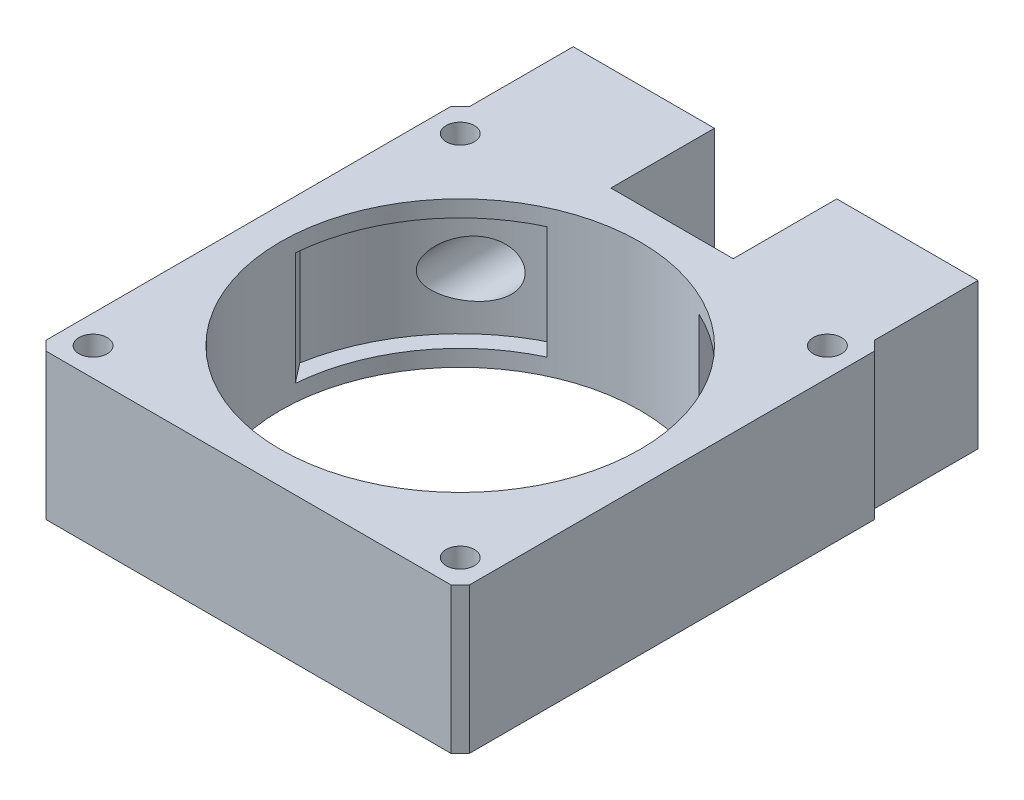
SolidWorks part; units mm, degrees
ref_plane "前视基准面" through (0, 0, 0) normal (0, 0, 1) x (1, 0, 0)
ref_plane "上视基准面" through (0, 0, 0) normal (0, 1, 0) x (1, 0, 0)
ref_plane "右视基准面" through (0, 0, 0) normal (1, 0, 0) x (0, 0, -1)
sketch "草图1" plane through (0, 0, 0) normal (0, 1, 0) x (1, 0, 0)
  line L1 (-22.5, -22.5) -> (22.5, -22.5)
  line L2 (-22.5, -22.5) -> (-22.5, 22.5)
  line L3 (-22.5, 22.5) -> (22.5, 22.5)
  line L4 (22.5, -22.5) -> (22.5, 22.5)
  line L5 (-22.5, -22.5) -> (22.5, 22.5) construction
  line L6 (-22.5, 22.5) -> (22.5, -22.5) construction
  point P0 (0, 0)
  dimension "D1" = 45
  dimension "D2" = 45
extrude "凸台-拉伸1" add sketch "草图1" along normal blind 15.5
sketch "草图2" plane through (0, 15.5, 0) normal (0, 1, 0) x (1, 0, 0)
  circle A0 centre (0, 0) radius 19.1
  dimension "D1" = 38.2
extrude "切除-拉伸1" cut sketch "草图2" against normal through all
sketch "草图3" plane through (0, 15.5, 0) normal (0, 1, 0) x (1, 0, 0)
  circle A0 centre (0, 0) radius 20
  circle A1 centre (0, 0) radius 21.5
  dimension "D1" = 40
  dimension "D2" = 43
extrude "切除-拉伸2" [suppressed] cut sketch "草图3" against normal blind 0.4
sketch "草图4" plane through (0, 0, 0) normal (0, -1, 0) x (1, 0, 0)
  circle A1 centre (0, 0) radius 21.5
  circle A2 centre (0, 0) radius 21.5
  circle A3 centre (0, 0) radius 20
  circle A4 centre (0, 0) radius 20
  dimension "D1" = 0
  dimension "D2" = 0
extrude "切除-拉伸3" [suppressed] cut sketch "草图4" against normal blind 0.4
sketch "草图5" plane through (0, 0, -22.5) normal (0, 0, -1) x (-1, 0, 0)
  line L0 (0, 15.5) -> (0, 0) construction
  line L1 (-22.5, 15.5) -> (22.5, 15.5) construction
  line L2 (-14, 15.5) -> (-14, 0) construction
  line L3 (-22.5, 0) -> (22.5, 0) construction
  line L4 (21.5, 15.5) -> (6.5, 15.5)
  line L5 (-21.5, 0) -> (-6.5, 0)
  line L6 (-21.5, 0) -> (-21.5, 15.5)
  line L7 (-21.5, 15.5) -> (-6.5, 15.5)
  line L8 (-6.5, 0) -> (-6.5, 15.5)
  line L9 (-21.5, 0) -> (-6.5, 15.5) construction
  line L10 (-21.5, 15.5) -> (-6.5, 0) construction
  line L11 (6.5, 0) -> (6.5, 15.5)
  line L12 (21.5, 0) -> (6.5, 0)
  line L13 (21.5, 0) -> (21.5, 15.5)
  point P9 (-14, 7.75)
  dimension "D1" = 15
  dimension "D2" = 14
extrude "凸台-拉伸2" add sketch "草图5" along normal blind 12
sketch "草图6" plane through (0, 0, -34.5) normal (0, 0, -1) x (-1, 0, 0)
  line L0 (-14, 15.5) -> (-14, 0) construction
  line L1 (-6.5, 15.5) -> (-21.5, 15.5) construction
  line L2 (-21.5, 0) -> (-6.5, 0) construction
  line L3 (-21.5, 7.75) -> (-6.5, 7.75) construction
  line L4 (-21.5, 15.5) -> (-21.5, 0) construction
  line L5 (-6.5, 0) -> (-6.5, 15.5) construction
  line L6 (0, 15.5) -> (0, 0) construction
  line L7 (-6.5, 15.5) -> (6.5, 15.5) construction
  circle A0 centre (-14, 7.75) radius 3
  circle A1 centre (14, 7.75) radius 3
  dimension "D1" = 6
extrude "切除-拉伸4" cut sketch "草图6" against normal blind 35
sketch "草图7" plane through (0, 15.5, 0) normal (0, 1, 0) x (1, 0, 0)
  line L0 (-21.5, 22.5) -> (-22.5, 22.5) construction
  line L1 (-22.5, 22.5) -> (-22.5, -22.5) construction
  line L2 (0, 22.5) -> (0, -22.5) construction
  line L3 (6.5, 22.5) -> (-6.5, 22.5) construction
  line L4 (-22.5, -22.5) -> (22.5, -22.5) construction
  line L5 (-22.5, 0) -> (22.5, 0) construction
  line L6 (22.5, -22.5) -> (22.5, 22.5) construction
  circle A0 centre (-19.5, 19.5) radius 1.5
  circle A1 centre (19.5, 19.5) radius 1.5
  circle A2 centre (19.5, -19.5) radius 1.5
  circle A3 centre (-19.5, -19.5) radius 1.5
  dimension "D1" = 3
  dimension "D2" = 3
  dimension "D3" = 3
extrude "切除-拉伸5" cut sketch "草图7" against normal through all
ref_plane "基准面1" through (0, 7.75, 0) normal (0, -1, 0) x (-1, 0, 0)
sketch "草图8" plane through (0, 7.75, 0) normal (0, -1, 0) x (-1, 0, 0)
  line L0 (0, 0) -> (0, 22.5) construction
  line L1 (-6.5, 22.5) -> (6.5, 22.5) construction
  line L2 (0, 0) -> (-8.875, 19.0325) construction
  line L3 (-20.681, 3.6466) -> (0, 0) construction
  line L4 (-8.875, 19.0325) -> (-8.072, 17.3105)
  line L5 (-20.681, 3.6466) -> (-18.8098, 3.3167)
  line L6 (20.681, 3.6466) -> (18.8098, 3.3167)
  line L7 (8.875, 19.0325) -> (8.072, 17.3105)
  arc A0 (-8.072, 17.3105) -> (-18.8098, 3.3167) centre (0, 0) ccw
  circle A1 centre (0, 0) radius 19.1 construction
  arc A2 (-8.875, 19.0325) -> (-20.681, 3.6466) centre (0, 0) ccw
  arc A3 (8.875, 19.0325) -> (20.681, 3.6466) centre (0, 0) cw
  arc A4 (8.072, 17.3105) -> (18.8098, 3.3167) centre (0, 0) cw
  dimension "D1" = 21
  dimension "D2" = 25
  dimension "D3" = 80
extrude "切除-拉伸6" cut sketch "草图8" against normal blind 6 and the other way blind 6
sketch "草图9" plane through (0, 0, -34.5) normal (0, 0, -1) x (-1, 0, 0)
  circle A0 centre (-14, 7.75) radius 4.25
  circle A1 centre (14, 7.75) radius 4.25
  dimension "D1" = 8.5
  dimension "D2" = 8.5
extrude "切除-拉伸7" cut sketch "草图9" against normal blind 12
chamfer "倒角1" distance 2 angle 45 2 edges at (-18.8098, 7.75, -3.3167) (18.8098, 7.75, -3.3167)
chamfer "倒角2" distance 1 angle 45 4 edges at (22.5, 7.75, 22.5) (-22.5, 7.75, 22.5) (-22.5, 7.75, -22.5) (22.5, 7.75, -22.5)
chamfer "倒角3" distance 1 angle 45 2 edges at (-18.25, 7.75, -22.5) (9.75, 7.75, -22.5)
chamfer "倒角4" distance 1 angle 45 8 edges at (-14, 0, -34.5) (-21.5, 7.75, -34.5) (-14, 15.5, -34.5) (-6.5, 7.75, -34.5) (14, 0, -34.5) (6.5, 7.75, -34.5) (14, 15.5, -34.5) (21.5, 7.75, -34.5)
